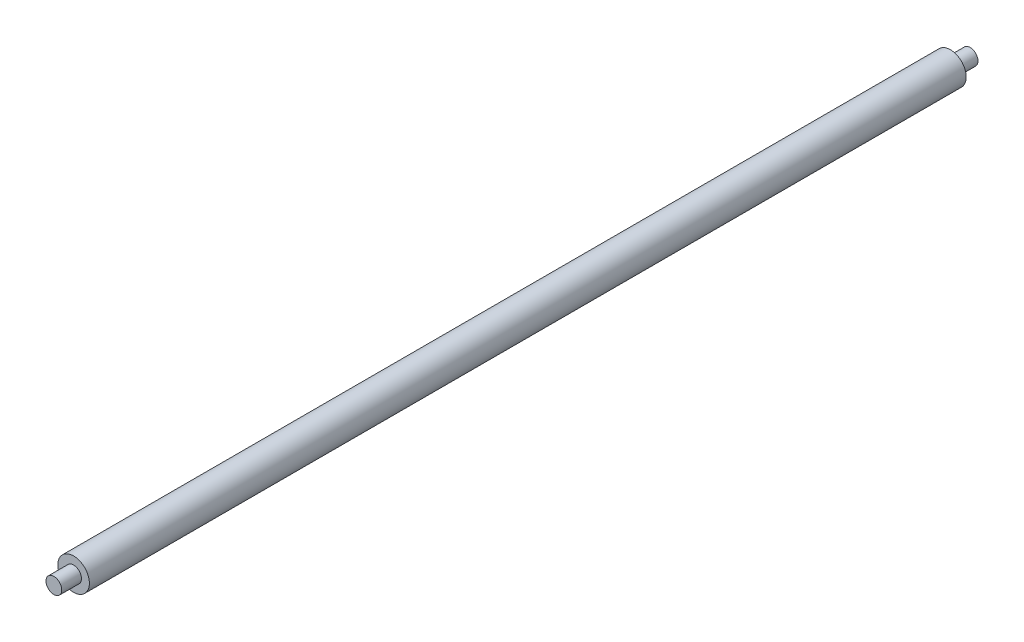
SolidWorks part; units mm, degrees
ref_plane "Front Plane" through (0, 0, 0) normal (0, 0, 1) x (1, 0, 0)
ref_plane "Top Plane" through (0, 0, 0) normal (0, 1, 0) x (1, 0, 0)
ref_plane "Right Plane" through (0, 0, 0) normal (1, 0, 0) x (0, 0, -1)
sketch "Sketch1" plane through (0, 0, 0) normal (0, 0, 1) x (1, 0, 0)
  circle A0 centre (0, 0) radius 6
  dimension "D1" = 12
extrude "Boss-Extrude1" add sketch "Sketch1" along normal mid plane 333.5
sketch "Sketch2" plane through (0, 0, 166.75) normal (0, 0, 1) x (1, 0, 0)
  circle A0 centre (0, 0) radius 3
  dimension "D1" = 6
extrude "Boss-Extrude2" add sketch "Sketch2" along normal blind 7.5
sketch "Sketch3" plane through (0, 0, -166.75) normal (0, 0, -1) x (-1, 0, 0)
  circle A0 centre (0, 0) radius 3
  dimension "D1" = 6
extrude "Boss-Extrude3" add sketch "Sketch3" along normal blind 7.5
